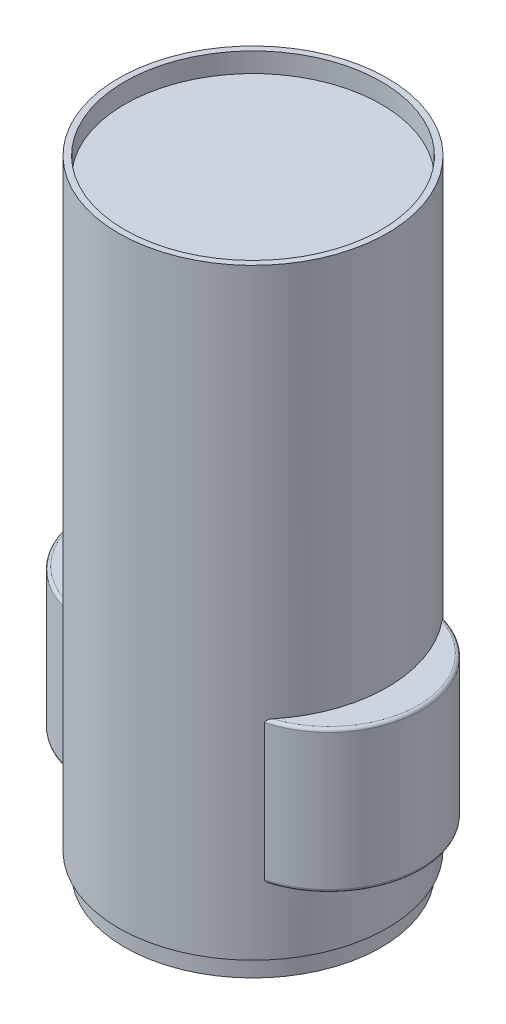
SolidWorks part; units mm, degrees
ref_plane "Front Plane" through (0, 0, 0) normal (0, 0, 1) x (1, 0, 0)
ref_plane "Top Plane" through (0, 0, 0) normal (0, 1, 0) x (1, 0, 0)
ref_plane "Right Plane" through (0, 0, 0) normal (1, 0, 0) x (0, 0, -1)
sketch "Sketch1" plane through (0, 0, 0) normal (1, 0, 0) x (0, 0, -1)
  line L0 (0, 0) -> (-42.5, 0)
  line L1 (-42.5, 0) -> (-42.5, 6.5)
  line L2 (-42.5, 6.5) -> (-44.5, 6.5)
  line L3 (-44.5, 6.5) -> (-44.5, 205.8)
  line L4 (-44.5, 205.8) -> (-42.5, 205.8)
  line L5 (-42.5, 205.8) -> (-42.5, 199.3)
  line L6 (-42.5, 199.3) -> (0, 199.3)
  line L7 (0, 199.3) -> (0, 0)
  line L8 (0, 29.9719) -> (0, 40.8779) construction
  dimension "D1" = 89
  dimension "D2" = 6.5
  dimension "D3" = 85
  dimension "D4" = 199.3
revolve "Revolve1" add sketch "Sketch1" angle 360 about L7
ref_plane "Plane1" through (0, 28.5, 0) normal (0, -1, 0) x (1, 0, 0)
sketch "Sketch2" plane through (0, 28.5, 0) normal (0, -1, 0) x (1, 0, 0)
  line L0 (25.15, 0) -> (-25.15, 0) construction
  arc A0 (0, -17.4309) -> (0, 17.4309) centre (25.15, 0) ccw
  arc A1 (0, 17.4309) -> (0, -17.4309) centre (-25.15, 0) ccw
  dimension "D2" = 61.2
  dimension "D1" = 50.3
extrude "Extrude1" add sketch "Sketch2" against normal blind 47.07
sketch "Sketch3" plane through (0, 75.57, 0) normal (0, 1, 0) x (-1, 0, 0)
  line L0 (48.03, 5) -> (48.03, -5)
  line L2 (48.03, 0) -> (20.5452, 0) construction
  arc A0 (48.03, -5) -> (44.9068, -5.0935) centre (46.467, -5) cw
  arc A2 (44.9068, 5.0935) -> (48.03, 5) centre (46.467, 5) cw
  arc A4 (44.9068, -5.0935) -> (44.2097, -5.0746) centre (44.5574, -5.1145) ccw
  circle A5 centre (0, 0) radius 44.5 construction
  arc A6 (44.2097, -5.0746) -> (44.2097, 5.0746) centre (0, 0) ccw
  arc A7 (44.9068, 5.0935) -> (44.2097, 5.0746) centre (44.5574, 5.1145) cw
  dimension "D2" = 10
  dimension "D3" = 1.563
  dimension "D4" = 0.7
  dimension "D1" = 48.03
extrude "Extrude2" add sketch "Sketch3" along normal blind 100
fillet "Fillet1" radius 1 4 edges at (55.75, 28.5, 0) (55.75, 75.57, 0) (-55.75, 28.5, 0) (-55.75, 75.57, 0)
ref_point "Point1"
ref_axis "Axis1" through (0, -0.0391, 0) along (0, 1, 0)
ref_axis "Axis2" through (-86.7713, 0, 0) along (1, 0, 0)
ref_point "Point2"
